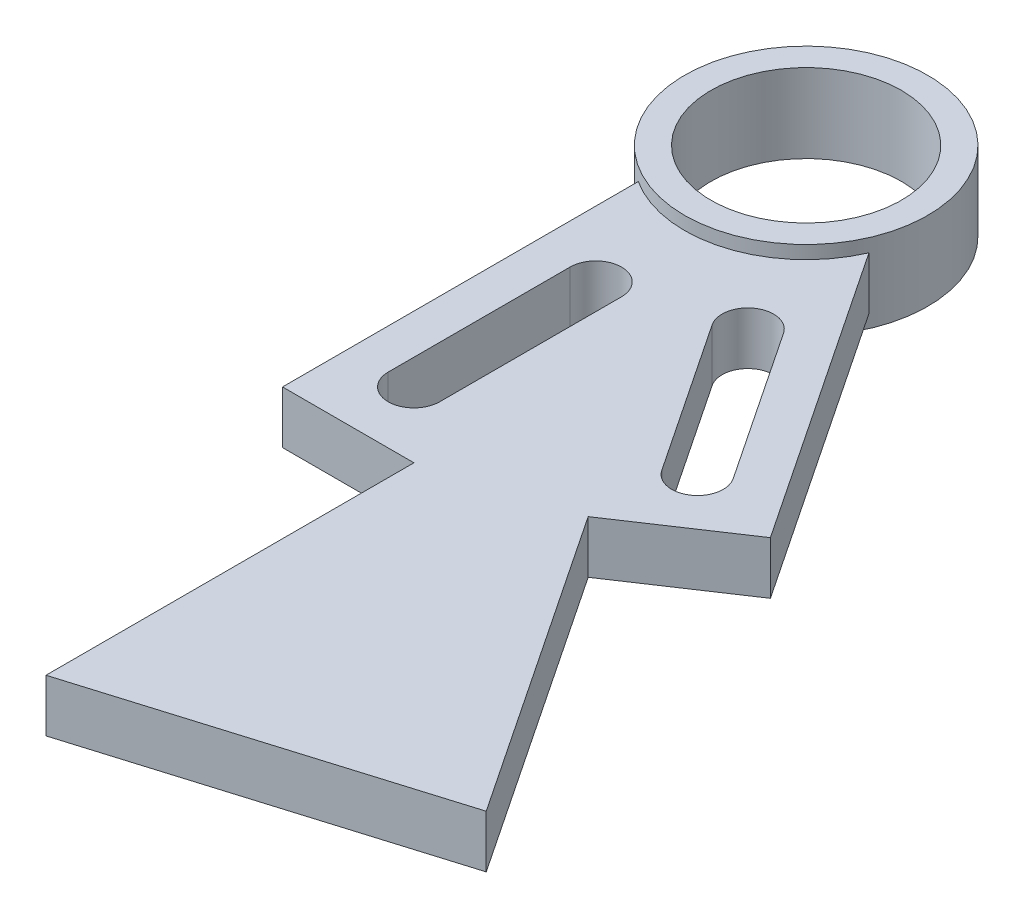
SolidWorks part; units mm, degrees
material "AISI 4130 Steel, normalized at 870C"
ref_plane "Front Plane" through (0, 0, 0) normal (0, 0, 1) x (1, 0, 0)
ref_plane "Top Plane" through (0, 0, 0) normal (0, 1, 0) x (1, 0, 0)
ref_plane "Right Plane" through (0, 0, 0) normal (1, 0, 0) x (0, 0, -1)
sketch "Sketch1" plane through (0, 0, 0) normal (0, 1, 0) x (1, 0, 0)
  line L0 (0, -50.4952) -> (0, -14.6812) construction
  line L1 (28.0186, -42.0086) -> (8.1463, -12.2138) construction
  line L2 (0, -47.3837) -> (0, -25.4127) construction
  line L5 (-3.1115, -47.3837) -> (-3.1115, -25.4127)
  line L8 (-7.9375, -55.3212) -> (7.9375, -55.3212)
  line L9 (24.093, -50.4278) -> (37.2999, -41.6192)
  line L10 (-7.9375, -55.3212) -> (-7.9375, -12.3505)
  line L11 (37.2999, -41.6192) -> (13.4564, -5.8704)
  line L12 (7.9375, -55.3212) -> (7.9375, -99.7712)
  line L13 (24.093, -50.4278) -> (48.7572, -87.4073)
  line L14 (7.9375, -99.7712) -> (48.7572, -87.4073)
  line L15 (0, -14.6812) -> (0, 0) construction
  line L16 (0, -55.3212) -> (0, -50.4952) construction
  line L17 (30.6964, -46.0235) -> (28.0186, -42.0086)
  line L18 (3.1115, -47.3837) -> (3.1115, -25.4127)
  line L19 (14.1009, -21.1417) -> (26.2921, -39.42) construction
  line L20 (16.6895, -19.4152) -> (28.8807, -37.6936)
  line L21 (11.5124, -22.8682) -> (23.7035, -41.1465)
  line L22 (8.1463, -12.2138) -> (0, 0) construction
  line L23 (0, 0) -> (19.144, -63.2043) construction
  line L25 (175.0141, -262.4006) -> (14.541, -21.8014) construction
  line L27 (0, 0) -> (28.3474, -93.5892) construction
  circle A0 centre (0, 0) radius 11.5062
  circle A1 centre (0, 0) radius 14.6812
  arc A2 (-3.1115, -47.3837) -> (3.1115, -47.3837) centre (0, -47.3837) ccw
  arc A3 (3.1115, -25.4127) -> (-3.1115, -25.4127) centre (0, -25.4127) ccw
  arc A4 (16.6895, -19.4152) -> (11.5124, -22.8682) centre (14.1009, -21.1417) ccw
  arc A5 (23.7035, -41.1465) -> (28.8807, -37.6936) centre (26.2921, -39.42) ccw
  point P9 (0, -36.3982)
  point P14 (20.1965, -30.2809)
  point P23 (0, -55.3212)
  point P26 (30.6964, -46.0235)
  point P33 (0, -50.4952)
  point P36 (28.0186, -42.0086)
  point P38 (0, -22.3012)
  dimension "D2" = 29.3624
  dimension "D3" = 40.64
  dimension "D4" = 4.826
  dimension "D6" = 44.45
  dimension "D7" = 7.9375
  dimension "D5" = 4.826
  dimension "D8" = 7.62
  dimension "D9" = 66.04
extrude "Bearing extrude" add sketch "Sketch1" along normal mid plane 9.525 contours A1 A0 region at (-6.8368, 0, -12.521)
extrude "Boss-Extrude2" add sketch "Sketch1<5>" along normal mid plane 6.35 contours A1 L10 L8 L12 L14 L13 L9 L11 A4 A2 region at (16.9968, 0, 56.1152)
sketch "Sketch1<5>" plane through (0, 0, 0) normal (0, 1, 0) x (1, 0, 0) same geometry as "Sketch1"
sketch3d "Tab Point"
  line L0 (19.144, 0, 63.2043) -> (19.144, 25.4, 63.2043) construction
  line L1 (0, 0, 0) -> (19.144, 0, 63.2043) construction
  line L2 (0, 0, 0) -> (28.3474, 0, 93.5892) construction
  dimension "D1" = 25.4
equation "\"Apex_thickness\"= .25"
equation "\"Bearing_diameter\"= .906"
equation "\"A-arm_angle\"= 32.91"
equation "\"D1@Sketch1\"=\"Bearing_diameter\""
equation "\"D1@Boss-Extrude2\"= \"Apex_thickness\""
equation "\"apex slot\"= 1.4"
equation "\"tube diameter\"= 5 / 8"
